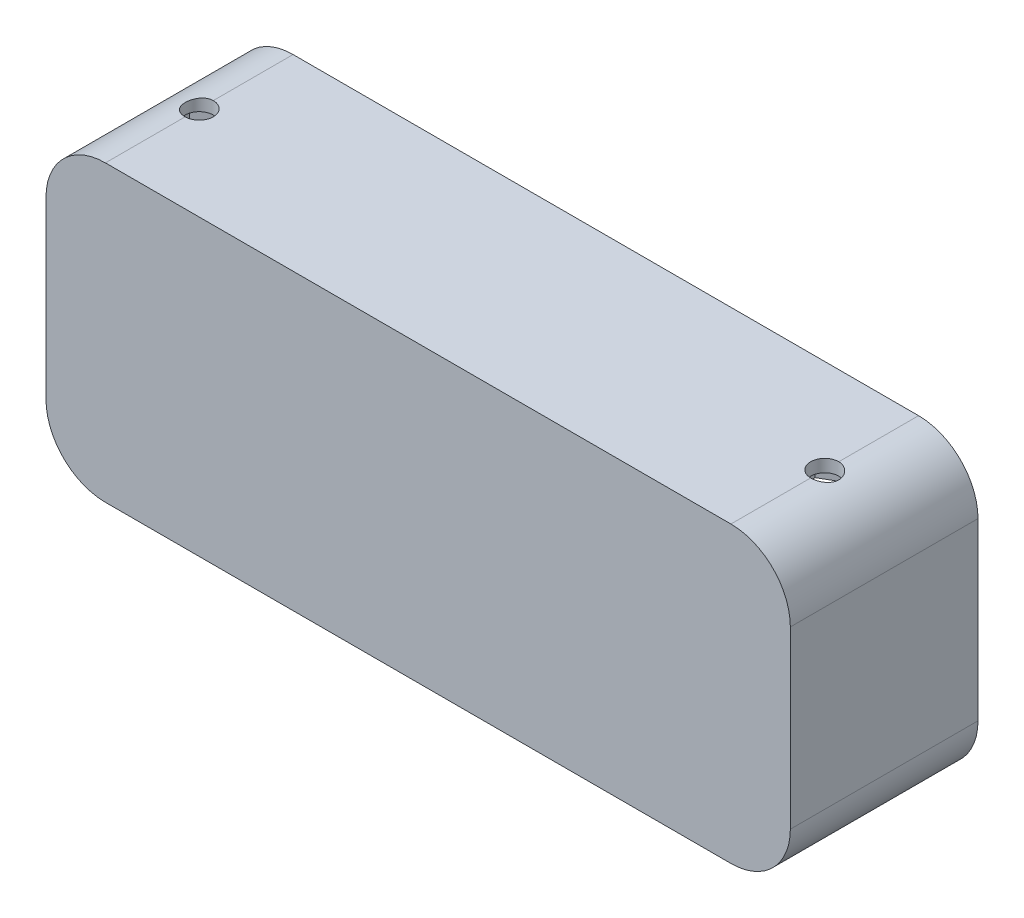
SolidWorks part; units mm, degrees
ref_plane "Front Plane" through (0, 0, 0) normal (0, 0, 1) x (1, 0, 0)
ref_plane "Top Plane" through (0, 0, 0) normal (0, 1, 0) x (1, 0, 0)
ref_plane "Right Plane" through (0, 0, 0) normal (1, 0, 0) x (0, 0, -1)
sketch "Sketch2" plane through (0, 0, 0) normal (0, 0, 1) x (1, 0, 0)
  line L0 (-36, 23.5) -> (-36, -19.5)
  line L1 (-50, -23.5) -> (50, -23.5)
  line L2 (-59.5, -14) -> (-59.5, 14)
  line L3 (-50, 23.5) -> (-36, 23.5)
  line L4 (59.5, -14) -> (59.5, 14)
  line L5 (-59.5, -23.5) -> (59.5, 23.5) construction
  line L6 (-59.5, 23.5) -> (59.5, -23.5) construction
  line L7 (-36, -19.5) -> (-24, -19.5)
  line L8 (-24, -19.5) -> (-24, 23.5)
  line L9 (-50, 19.5) -> (-40, 19.5)
  line L10 (55.5, -14) -> (55.5, 14)
  line L11 (-50, -19.5) -> (-40, -19.5)
  line L12 (-55.5, -14) -> (-55.5, 14)
  line L13 (-40, 19.5) -> (-40, -19.5)
  line L14 (-40, -23.5) -> (-20, -23.5)
  line L15 (-20, -19.5) -> (-20, 19.5)
  line L16 (-20, 19.5) -> (50, 19.5)
  line L17 (-40, 23.5) -> (-40, -23.5) construction
  line L18 (-24, 23.5) -> (50, 23.5)
  line L19 (-50, 19.5) -> (50, 19.5) construction
  line L20 (-20, -19.5) -> (50, -19.5)
  line L21 (-50, 23.5) -> (50, 23.5) construction
  line L22 (-20, -23.5) -> (-20, 23.5) construction
  line L23 (-36, -19.5) -> (-24, -19.5)
  line L24 (-50, -19.5) -> (50, -19.5) construction
  line L25 (-40, -19.5) -> (20.1318, -19.362)
  arc A0 (-50, -23.5) -> (-59.5, -14) centre (-50, -14) cw
  arc A1 (50, -23.5) -> (59.5, -14) centre (50, -14) ccw
  arc A2 (50, 23.5) -> (59.5, 14) centre (50, 14) cw
  arc A3 (-59.5, 14) -> (-50, 23.5) centre (-50, 14) cw
  arc A4 (50, 19.5) -> (55.5, 14) centre (50, 14) cw
  arc A5 (50, -19.5) -> (55.5, -14) centre (50, -14) ccw
  arc A6 (-50, -19.5) -> (-55.5, -14) centre (-50, -14) cw
  arc A7 (-55.5, 14) -> (-50, 19.5) centre (-50, 14) cw
  point P0 (0, 0)
  dimension "D3" = 9.5
  dimension "D1" = 119
  dimension "D2" = 47
  dimension "D4" = 10
  dimension "D5" = 12
  dimension "D6" = 43
  dimension "D7" = 4
  dimension "D8" = 4
extrude "Boss-Extrude1" add sketch "Sketch2" along normal blind 28 contours A3 L2 A0 L1 A1 L4 A2 L18 L8 L7 L0 L3 A5 L20 L15 L16 A4 L10 L12 A7 L9 L13 L11 A6 region at (-37.2795, 2.0046, 0)
sketch "Sketch3" plane through (-36, 0, 0) normal (1, 0, 0) x (0, 0, -1)
  line L0 (-14, 23.5) -> (-14, -20.5) construction
  line L1 (-28, 23.5) -> (0, 23.5) construction
  line L2 (-14, 1.5) -> (-29.5, 17) construction
  circle A0 centre (-14, 1.5) radius 2.75
  point P17 (-21.5, 1.5)
  dimension "D1" = 5.5
  dimension "D2" = 22
  dimension "D3" = 15.5
  dimension "D4" = 45
extrude "Cut-Extrude1" cut sketch "Sketch3" against normal blind 52 and the other way blind 19
sketch "Sketch4" plane through (0, 0, 28) normal (0, 0, 1) x (1, 0, 0)
  line L1 (50, 23.5) -> (-36, 23.5)
  line L8 (-59.5, 14) -> (-59.5, -14)
  line L9 (-50, -23.5) -> (50, -23.5)
  line L10 (59.5, -14) -> (59.5, 14)
  line L11 (50, 23.5) -> (-24, 23.5)
  line L13 (-24, 23.5) -> (-24, -19.5)
  line L14 (-24, -19.5) -> (-36, -19.5)
  line L15 (-36, -19.5) -> (-36, 23.5)
  line L16 (-59.5, 14) -> (-59.5, -14)
  line L17 (-50, -23.5) -> (50, -23.5)
  line L18 (59.5, -14) -> (59.5, 14)
  line L19 (-36, 23.5) -> (-50, 23.5)
  line L20 (-36, 23.5) -> (-50, 23.5)
  arc A4 (-50, 23.5) -> (-59.5, 14) centre (-50, 14) ccw
  arc A5 (-59.5, -14) -> (-50, -23.5) centre (-50, -14) ccw
  arc A6 (50, -23.5) -> (59.5, -14) centre (50, -14) ccw
  arc A7 (59.5, 14) -> (50, 23.5) centre (50, 14) ccw
  arc A8 (-50, 23.5) -> (-59.5, 14) centre (-50, 14) ccw
  arc A9 (-59.5, -14) -> (-50, -23.5) centre (-50, -14) ccw
  arc A10 (50, -23.5) -> (59.5, -14) centre (50, -14) ccw
  arc A11 (59.5, 14) -> (50, 23.5) centre (50, 14) ccw
  dimension "D1" = 0
extrude "Boss-Extrude2" add sketch "Sketch4" along normal blind 2
sketch "Sketch5" plane through (0, 23.5, 0) normal (0, 1, 0) x (1, 0, 0)
  line L0 (-50, -30) -> (-50, -20) construction
  line L1 (-50, -30) -> (-50, 0) construction
  line L2 (-50, -20) -> (-50, -10) construction
  line L3 (-50, -10) -> (-50, 0) construction
  circle A0 centre (-50, -15) radius 2.25
  dimension "D2" = 4.5
  dimension "D1" = 30
extrude "Cut-Extrude2" cut sketch "Sketch5" against normal blind 50
sketch "Sketch6" plane through (0, -19.5, 0) normal (0, 1, 0) x (1, 0, 0)
  line L1 (-50, -19.2724) -> (-46.3, -17.1362)
  line L2 (-46.3, -17.1362) -> (-46.3, -12.8638)
  line L3 (-46.3, -12.8638) -> (-50, -10.7276)
  line L4 (-50, -10.7276) -> (-53.7, -12.8638)
  line L5 (-53.7, -12.8638) -> (-53.7, -17.1362)
  line L6 (-53.7, -17.1362) -> (-50, -19.2724)
  circle A0 centre (-50, -15) radius 3.7 construction
  dimension "D1" = 7.4
extrude "Cut-Extrude3" cut sketch "Sketch6" against normal blind 2 and the other way blind 2
mirror "Mirror1" about plane through (0, 0, 0) normal (1, 0, 0) of "Cut-Extrude2"
mirror "Mirror2" about plane through (0, 0, 0) normal (0, 1, 0) of "Cut-Extrude3"
mirror "Mirror3" about plane through (0, 0, 0) normal (1, 0, 0) of "Mirror2"
sketch "Sketch7" plane through (-59.5, 0, 0) normal (-1, 0, 0) x (0, 0, 1)
  circle A0 centre (14, 1.5) radius 7.5
  dimension "D1" = 15
extrude "Cut-Extrude4" cut sketch "Sketch7" against normal blind 10
sketch "Sketch8" plane through (-20, 0, 0) normal (1, 0, 0) x (0, 0, -1)
  line L1 (-9.0925, 1.5) -> (-11.5463, 5.75)
  line L2 (-11.5463, 5.75) -> (-16.4537, 5.75)
  line L3 (-16.4537, 5.75) -> (-18.9075, 1.5)
  line L4 (-18.9075, 1.5) -> (-16.4537, -2.75)
  line L5 (-16.4537, -2.75) -> (-11.5463, -2.75)
  line L6 (-11.5463, -2.75) -> (-9.0925, 1.5)
  line L7 (-5.6284, 1.5) -> (-9.8142, 8.75)
  line L8 (-9.8142, 8.75) -> (-18.1858, 8.75)
  line L9 (-18.1858, 8.75) -> (-22.3716, 1.5)
  line L10 (-22.3716, 1.5) -> (-18.1858, -5.75)
  line L11 (-18.1858, -5.75) -> (-9.8142, -5.75)
  line L12 (-9.8142, -5.75) -> (-5.6284, 1.5)
  circle A0 centre (-14, 1.5) radius 4.25 construction
  circle A1 centre (-14, 1.5) radius 7.25 construction
  dimension "D1" = 8.5
  dimension "D2" = 3
extrude "Boss-Extrude3" add sketch "Sketch8" along normal blind 4
chamfer "Chamfer1" distance 4 angle 45 6 edges at (-20, 5.125, 7.7213) (-20, 8.75, 14) (-20, 5.125, 20.2787) (-20, -2.125, 20.2787) (-20, -5.75, 14) (-20, -2.125, 7.7213)
sketch "Sketch9" plane through (-24, 0, 0) normal (-1, 0, 0) x (0, 0, 1)
  circle A0 centre (14, 1.5) radius 2.75
  circle A1 centre (14, 1.5) radius 3.3
  dimension "D1" = 6.6
extrude "Boss-Extrude4" add sketch "Sketch9" along normal blind 1.5
chamfer "Chamfer2" distance 1.5 angle 45 1 edges at (-24, 1.5, 17.3)
ref_plane "Plane1" through (-30, 0, 0) normal (1, 0, 0) x (0, 0, -1)
mirror "Mirror6" about plane through (-30, 0, 0) normal (1, 0, 0) of "Boss-Extrude4"
chamfer "Chamfer3" distance 1.5 angle 45 1 edges at (-36, 4.8, 14)
sketch "Sketch10" plane through (0, 0, 0) normal (0, 0, -1) x (-1, 0, 0)
  line L1 (24, 23.5) -> (40, 23.5)
  line L2 (24, 23.5) -> (24, 19.5)
  line L3 (24, 19.5) -> (40, 19.5)
  line L4 (40, 23.5) -> (40, 19.5)
extrude "Boss-Extrude5" add sketch "Sketch10" against normal up to surface (28 mm away) up to face at (-30, 2, 28)
